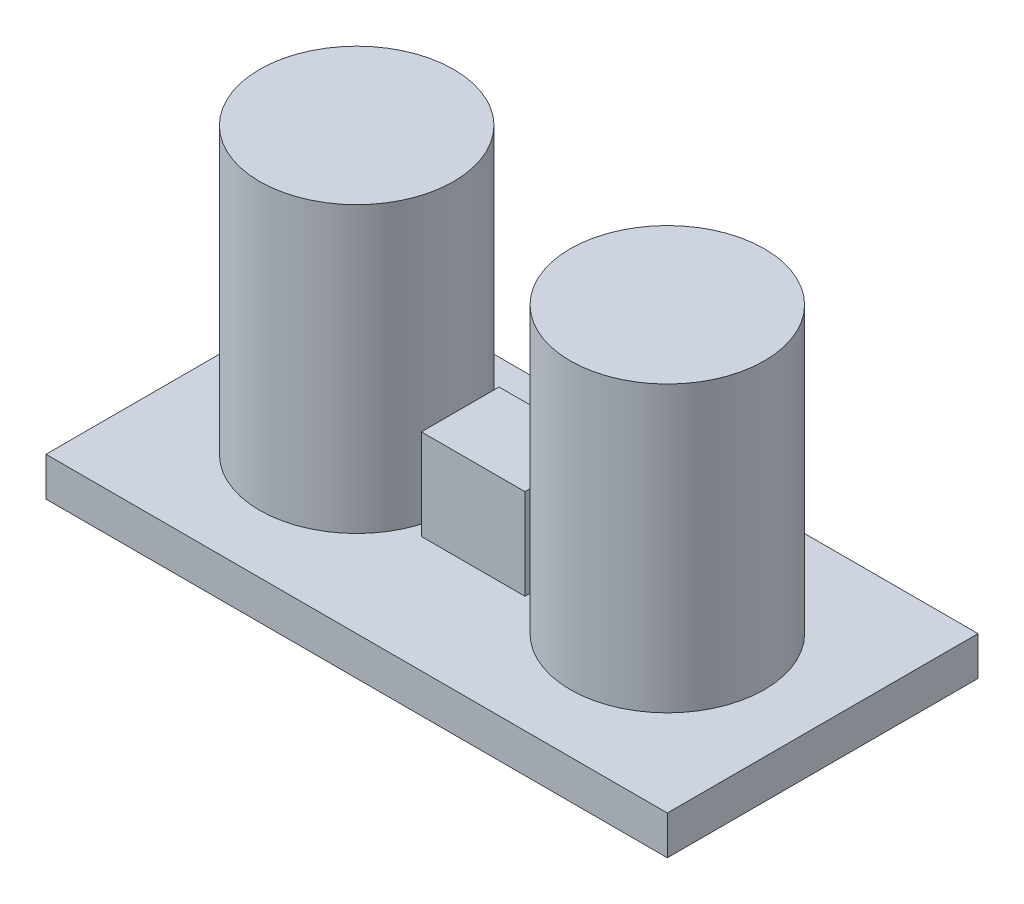
SolidWorks part; units mm, degrees
ref_plane "Front Plane" through (0, 0, 0) normal (0, 0, 1) x (1, 0, 0)
ref_plane "Top Plane" through (0, 0, 0) normal (0, 1, 0) x (1, 0, 0)
ref_plane "Right Plane" through (0, 0, 0) normal (1, 0, 0) x (0, 0, -1)
other "Configuration Table"
sketch "Sketch1" plane through (0, 0, 0) normal (0, 1, 0) x (1, 0, 0)
  line L1 (-4700, 400) -> (-2300, 400)
  line L2 (-4700, 400) -> (-4700, 1600)
  line L3 (-4700, 1600) -> (-2300, 1600)
  line L4 (-2300, 400) -> (-2300, 1600)
extrude "Boss-Extrude1" add sketch "Sketch1" along normal blind 150
sketch "Sketch2" plane through (0, 0, 0) normal (0, 1, 0) x (1, 0, 0)
  circle A0 centre (-4100, 1000) radius 375
extrude "Boss-Extrude2" add sketch "Sketch2" along normal blind 1100 from offset 150
sketch "Sketch3" plane through (0, 0, 0) normal (0, 1, 0) x (1, 0, 0)
  circle A0 centre (-2900, 1000) radius 375
extrude "Boss-Extrude3" add sketch "Sketch3" along normal blind 1100 from offset 150
sketch "Sketch4" plane through (0, 0, 0) normal (0, 1, 0) x (1, 0, 0)
  line L1 (-3700, 850) -> (-3300, 850)
  line L2 (-3700, 850) -> (-3700, 1150)
  line L3 (-3700, 1150) -> (-3300, 1150)
  line L4 (-3300, 850) -> (-3300, 1150)
extrude "Boss-Extrude4" add sketch "Sketch4" along normal blind 350 from offset 150
